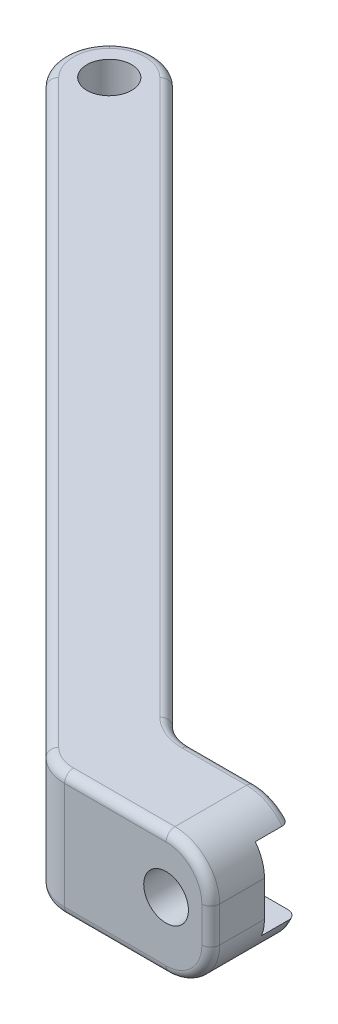
SolidWorks part; units mm, degrees
ref_plane "Front Plane" through (0, 0, 0) normal (0, 0, 1) x (1, 0, 0)
ref_plane "Top Plane" through (0, 0, 0) normal (0, 1, 0) x (1, 0, 0)
ref_plane "Right Plane" through (0, 0, 0) normal (1, 0, 0) x (0, 0, -1)
sketch "Sketch1" plane through (0, 0, 0) normal (0, 1, 0) x (1, 0, 0)
  line L0 (0, 7.0711) -> (-7.0711, 0)
  line L1 (0, 7.0711) -> (66.9211, -59.85)
  line L2 (-7.0711, 0) -> (62.7789, -69.85)
  line L4 (66.9211, -59.85) -> (81.2, -59.85)
  line L5 (81.2, -59.85) -> (81.2, -69.85)
  line L6 (81.2, -69.85) -> (62.7789, -69.85)
  circle A0 centre (0, 0) radius 2.5
  point P6 (76.2, -63.5)
  dimension "D1" = 5
  dimension "D2" = 5
  dimension "D3" = 5
  dimension "D4" = 10
  dimension "D5" = 69.85
  dimension "D6" = 45
  dimension "D7" = 10
  dimension "D8" = 5
  dimension "D9" = 76.2
  dimension "D10" = 63.5
extrude "Boss-Extrude1" add sketch "Sketch1" along normal blind 13.97
sketch "Sketch2" plane through (0, 0, 59.85) normal (0, 0, -1) x (-1, 0, 0)
  line L0 (-81.2, 13.97) -> (-81.2, 0) construction
  line L2 (-81.2, 13.97) -> (-66.9211, 13.97) construction
  circle A0 centre (-76.2, 7.62) radius 2.5
  dimension "D1" = 5
  dimension "D2" = 5
  dimension "D3" = 6.35
extrude "Cut-Extrude1" cut sketch "Sketch2" against normal up to next
sketch "Sketch3" plane through (0, 0, 59.85) normal (0, 0, -1) x (-1, 0, 0)
  line L0 (-78.3389, 11.995) -> (-84.7617, 11.995)
  line L1 (-71.1482, 7.62) -> (-73.6741, 11.995)
  line L2 (-73.6741, 11.995) -> (-78.7259, 11.995)
  line L3 (-78.7259, 11.995) -> (-81.2518, 7.62)
  line L4 (-81.2518, 7.62) -> (-78.7259, 3.245)
  line L5 (-78.7259, 3.245) -> (-73.6741, 3.245)
  line L6 (-73.6741, 3.245) -> (-71.1482, 7.62)
  line L7 (-84.7617, 11.995) -> (-84.7617, 3.245)
  line L8 (-78.7259, 3.245) -> (-84.7617, 3.245)
  circle A0 centre (-76.2, 7.62) radius 4.375 construction
  circle M7 centre (-76.2, 7.62) radius 2.5
  line M11 (-81.2, 13.97) -> (-81.2, 0)
  dimension "D1" = 8.75
extrude "Cut-Extrude2" cut sketch "Sketch3" against normal blind 4 contours L5 L6 L1 L2 L0 L3 L4 M11 M7 | L3 L0 M11 | L8 L4 M11 | L8 L4 L3 L0 L7 M11 | L3 L4 M11 region at (76.0065, 11.8617, 59.85) region at (80.3753, 10.5666, 59.85) region at (82.9811, 7.62, 59.85) region at (81.2173, 7.62, 59.85) region at (80.3753, 4.6734, 59.85)
fillet "Fillet1" radius 5 6 edges at (0, 6.985, -7.0711) (-7.0711, 6.985, 0) (81.2, 0, 64.85) (81.2, 13.97, 64.85) (62.7789, 6.985, 69.85) (66.9211, 6.985, 59.85)
fillet "Fillet2" radius 1 21 edges at (-5, 0, 0) (0, 0, -5) (34.4961, 0, 27.425) (67.0787, 0, 59.4694) (72.5961, 0, 59.85) (79.0482, 0.8906, 59.85) (78.422, 13.4491, 59.85) (72.5961, 13.97, 59.85) (67.0787, 13.97, 59.4694) (34.4961, 13.97, 27.425) (0, 13.97, -5) (-5, 13.97, 0) (28.8895, 13.97, 35.9605) (62.9366, 13.97, 69.4694) (70.525, 13.97, 69.85) (79.7355, 12.5055, 69.85) (81.2, 6.985, 69.85) (79.7355, 1.4645, 69.85) (70.525, 0, 69.85) (62.9366, 0, 69.4694) (28.8895, 0, 35.9605)
